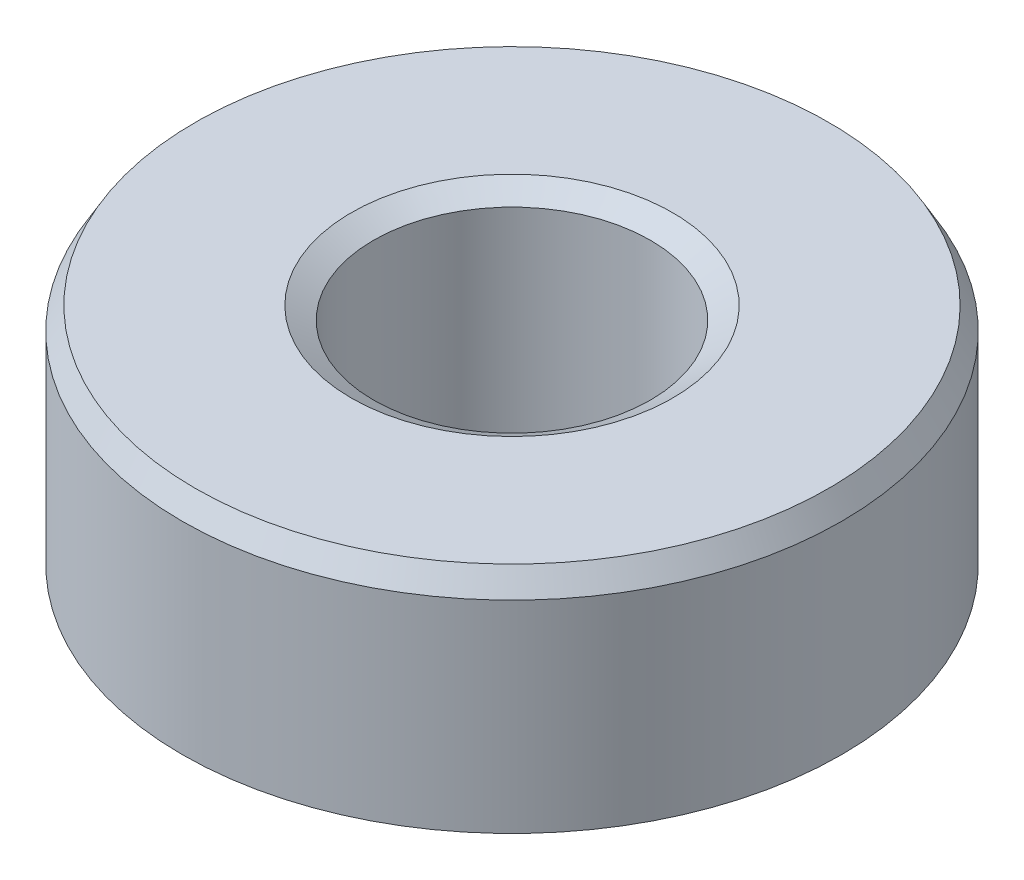
SolidWorks part; units mm, degrees
ref_plane "Front Plane" through (0, 0, 0) normal (0, 0, 1) x (1, 0, 0)
ref_plane "Top Plane" through (0, 0, 0) normal (0, 1, 0) x (1, 0, 0)
ref_plane "Right Plane" through (0, 0, 0) normal (1, 0, 0) x (0, 0, -1)
sketch "Sketch1" plane through (0, 0, 0) normal (0, 1, 0) x (1, 0, 0)
  circle A0 centre (0, 0) radius 50
  dimension "SLEEVE_OD" = 100
extrude "Boss-Extrude1" add sketch "Sketch1" along normal blind 35.9548
sketch "Sketch2" plane through (0, 0, 0) normal (0, 1, 0) x (1, 0, 0)
  circle A0 centre (0, 0) radius 20.9992
  dimension "BORE_D" = 41.9983
extrude "Cut-Extrude1" cut sketch "Sketch2" along normal through all
chamfer "Chamfer1" distance 3.3655 angle 30 4 edges at (0, 35.9548, 20.9992) (0, 0, 20.9992) (0, 0, 50) (0, 35.9548, 50) first distance on face at (0, 35.9548, 20.9992) first distance on face at (0, 0, 20.9992) first distance on face at (0, 35.9548, 50)
